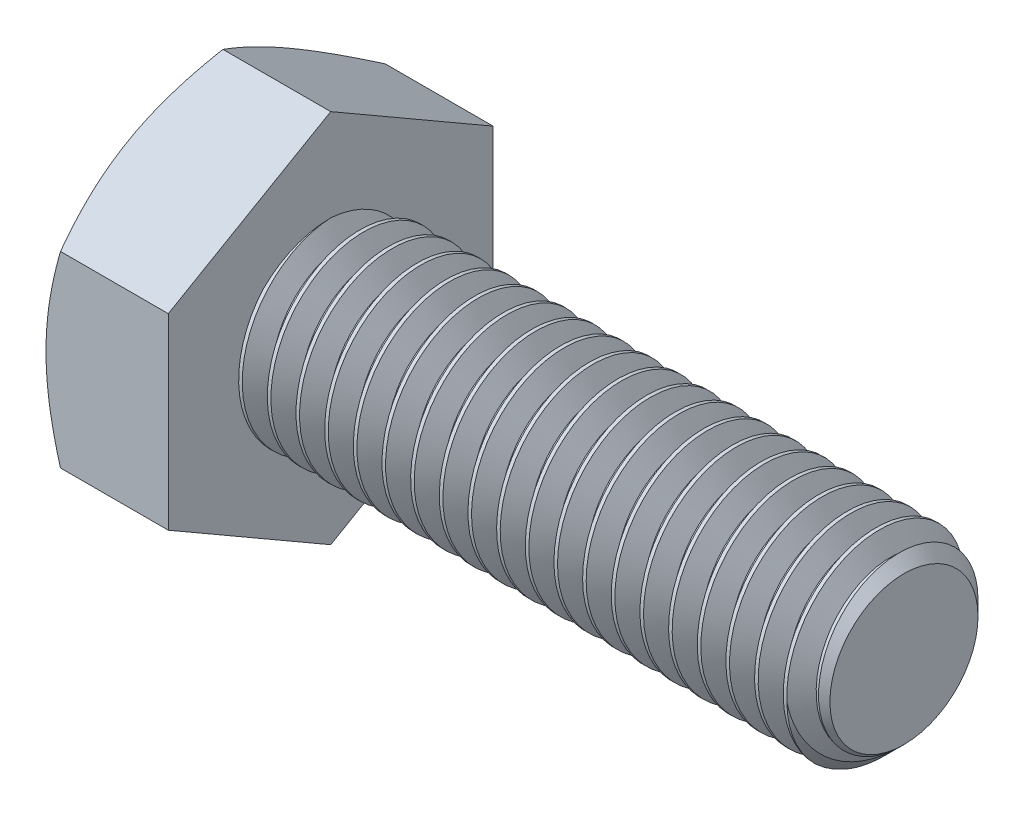
SolidWorks part; units mm, degrees
ref_plane "Front Plane" through (0, 0, 0) normal (0, 0, 1) x (1, 0, 0)
ref_plane "Top Plane" through (0, 0, 0) normal (0, 1, 0) x (1, 0, 0)
ref_plane "Right Plane" through (0, 0, 0) normal (1, 0, 0) x (0, 0, -1)
sketch "Sketch1" plane through (0, 0, 0) normal (0, 0, 1) x (1, 0, 0)
  line L0 (-18.2, 0) -> (18.2, 0) construction
  line L1 (-11.8, 8.5) -> (-11.8, -8.5) construction
  line L2 (-18.2, 8.5) -> (-18.2, -8.5) construction
  line L3 (18.2, 5) -> (18.2, -5) construction
  point P8 (12.95, -5)
  dimension "Thread Dia" = 10
  dimension "Hex" = 17
  dimension "Head Ht" = 6.4
  dimension "Length" = 30
  dimension "D1" = 5.25
ref_plane "Plane2" through (18.2, 0, 0) normal (1, 0, 0) x (0, 0, -1)
sketch "Sketch2" plane through (18.2, 0, 0) normal (1, 0, 0) x (0, 0, -1)
  circle A0 centre (0, 0) radius 5
extrude "Boss-Extrude1" add sketch "Sketch2" against normal up to vertex (30 mm away) up to point (-11.8, -8.5, 0)
sketch "Sketch4" plane through (18.2, 0, 0) normal (1, 0, 0) x (0, 0, -1)
  circle A1 centre (0, 0) radius 5
  circle A2 centre (0, 0) radius 5
  dimension "D1" = 0
curve "Helix/Spiral1" pitch 1.5 height 31.5 turns 21 parameters "Pitch"=1.5
chamfer "Chamfer1" distance 1.125 angle 45 1 edges at (18.2, 0, -5)
sketch "Sketch5" plane through (0, 0, 0) normal (0, 0, 1) x (1, 0, 0)
  line L0 (18.2, 5) -> (18.7625, 4.0257)
  line L1 (18.7625, 4.0257) -> (18.95, 4.0257)
  line L2 (18.95, 4.0257) -> (19.5125, 5)
  line L3 (18.2, 5) -> (19.5125, 5)
  line L4 (18.8562, 4.0257) -> (18.8562, 5) construction
  line L5 (18.4812, 4.5129) -> (19.2312, 4.5129) construction
  line L6 (18.2, -5) -> (18.2, 5) construction
  dimension "D1" = 60
  dimension "D2" = 0.1875
  dimension "D3" = 0.75
sweep "Cut-Sweep1" cut profiles "Sketch5" path "Helix/Spiral1"
sketch "Sketch3" plane through (-11.8, 0, 0) normal (-1, 0, 0) x (0, 0, 1)
  line L0 (0, 8.5) -> (0, -8.5) construction
  line L1 (-8.5, -4.9075) -> (0, -9.815)
  line L2 (0, -9.815) -> (8.5, -4.9075)
  line L3 (8.5, -4.9075) -> (8.5, 4.9075)
  line L4 (8.5, 4.9075) -> (0, 9.815)
  line L5 (0, 9.815) -> (-8.5, 4.9075)
  line L6 (-8.5, 4.9075) -> (-8.5, -4.9075)
  circle A0 centre (0, 0) radius 8.5 construction
extrude "Boss-Extrude2" add sketch "Sketch3" along normal up to vertex (6.4 mm away) up to point (-18.2, -8.5, 0)
sketch "Sketch6" plane through (-18.2, 0, 0) normal (-1, 0, 0) x (0, 0, 1)
  circle A0 centre (0, 0) radius 8.5 construction
  circle A1 centre (0, 0) radius 8.5
extrude "Cut-Extrude1" cut sketch "Sketch6" against normal through all draft 60 flip side to cut
sketch "Sketch9" plane through (0, 0, 0) normal (0, 0, 1) x (1, 0, 0)
  line L0 (-11.8, 5) -> (-11.8, 0)
  line L1 (-11.8, 0) -> (-30.8, 0)
  line L2 (-30.8, 0) -> (-35.8, 5)
  line L3 (-35.8, 5) -> (-11.8, 5)
  line L4 (-18.2, 0) -> (18.2, 0) construction
  line L5 (-11.8, 8.5) -> (-11.8, -8.5) construction
  line L6 (18.2, 5) -> (18.2, -5) construction
  dimension "D1" = 45
  dimension "MinThreadLg" = 54
revolve "Revolve1" [suppressed] add sketch "Sketch9" angle 360 about L1
equation "\"D2@Sketch5\" = \"Pitch@Helix/Spiral1\"*.125"
equation "\"D3@Sketch5\" = \"Pitch@Helix/Spiral1\"*.50"
equation "\"D3@Helix/Spiral1\" = \"Length@Sketch1\"+\"Pitch@Helix/Spiral1\""
equation "\"D1@Chamfer1\" = \"Pitch@Helix/Spiral1\"*.750"
equation "\"D1@Sketch1\" = \"Pitch@Helix/Spiral1\"*3.50"
